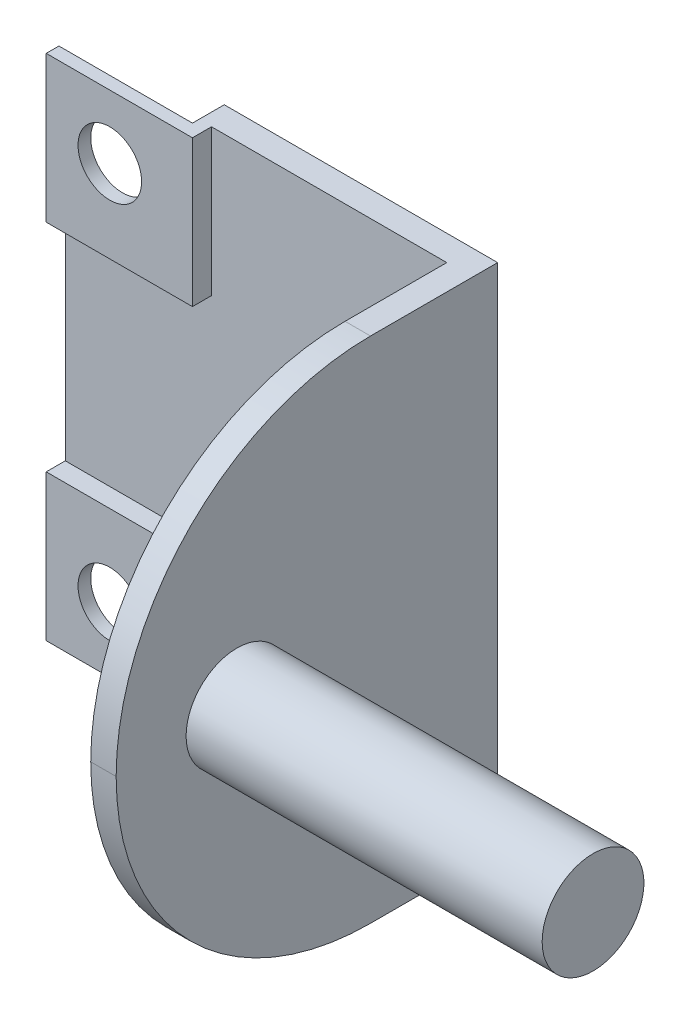
SolidWorks part; units mm, degrees
ref_plane "Plan de face" through (0, 0, 0) normal (0, 0, 1) x (1, 0, 0)
ref_plane "Plan de dessus" through (0, 0, 0) normal (0, 1, 0) x (1, 0, 0)
ref_plane "Plan de droite" through (0, 0, 0) normal (1, 0, 0) x (0, 0, -1)
sketch "Esquisse1" plane through (0, 0, 0) normal (0, 0, 1) x (1, 0, 0)
  line L1 (0, 0) -> (-32, 0)
  line L2 (0, 0) -> (0, 40)
  line L3 (0, 40) -> (-32, 40)
  line L4 (-32, 0) -> (-32, 40)
  dimension "D1" = 32
  dimension "D2" = 40
extrude "Boss.-Extru.1" add sketch "Esquisse1" along normal blind 2
sketch "Esquisse2" plane through (0, 0, 2) normal (0, 0, 1) x (1, 0, 0)
  line L0 (0, 40) -> (-32, 40) construction
  line L1 (0, 0) -> (-2, 0)
  line L2 (0, 0) -> (0, 40)
  line L3 (0, 40) -> (-2, 40)
  line L4 (-2, 0) -> (-2, 40)
  dimension "D1" = 2
extrude "Boss.-Extru.2" add sketch "Esquisse2" along normal blind 28
fillet "Congé1" radius 20 2 edges at (-1, 40, 30) (-1, 0, 30)
sketch "Esquisse3" plane through (0, 0, 0) normal (1, 0, 0) x (0, 0, -1)
  line L0 (0, 40) -> (0, 0) construction
  line L1 (-30, 20) -> (0, 20) construction
  circle A0 centre (-20.5, 20) radius 4
  dimension "D2" = 8
  dimension "D1" = 9.5
extrude "Enlèv. mat.-Extru.1" cut sketch "Esquisse3" against normal blind 30
sketch "Esquisse4" plane through (0, 0, 2) normal (0, 0, 1) x (1, 0, 0)
  line L0 (0, 20) -> (-32, 20) construction
  line L1 (-32, 40) -> (-21.5, 40)
  line L2 (-32, 40) -> (-32, 29.5)
  line L3 (-32, 29.5) -> (-21.5, 29.5)
  line L4 (-21.5, 40) -> (-21.5, 29.5)
  line L5 (-32, 40) -> (-32, 0) construction
  line L6 (-32, 10.5) -> (-21.5, 10.5)
  line L7 (-21.5, 0) -> (-21.5, 10.5)
  line L8 (-32, 0) -> (-21.5, 0)
  line L9 (-32, 0) -> (-32, 10.5)
  dimension "D1" = 10.5
  dimension "D2" = 10.5
extrude "Enlèv. mat.-Extru.2" cut sketch "Esquisse4" against normal blind 30
sketch "Esquisse5" plane through (0, 0, 2) normal (0, 0, 1) x (1, 0, 0)
  line L0 (0, 20) -> (-32, 20) construction
  line L1 (-21.5, 40) -> (-20.5, 40)
  line L2 (-21.5, 40) -> (-21.5, 28.5)
  line L3 (-21.5, 28.5) -> (-20.5, 28.5)
  line L4 (-20.5, 40) -> (-20.5, 28.5)
  line L5 (-32, 29.5) -> (-20.5, 29.5)
  line L6 (-32, 29.5) -> (-32, 28.5)
  line L7 (-32, 28.5) -> (-20.5, 28.5)
  line L8 (-20.5, 29.5) -> (-20.5, 28.5)
  line L9 (-32, 29.5) -> (-32, 10.5) construction
  line L10 (-21.5, 11.5) -> (-20.5, 11.5)
  line L11 (-20.5, 0) -> (-20.5, 11.5)
  line L12 (-21.5, 0) -> (-20.5, 0)
  line L13 (-21.5, 0) -> (-21.5, 11.5)
  line L14 (-32, 11.5) -> (-20.5, 11.5)
  line L15 (-20.5, 10.5) -> (-20.5, 11.5)
  line L16 (-32, 10.5) -> (-20.5, 10.5)
  line L17 (-32, 10.5) -> (-32, 11.5)
  line M7 (-21.5, 40) -> (-21.5, 29.5)
  line M8 (-21.5, 29.5) -> (-32, 29.5)
  line M9 (-32, 29.5) -> (-32, 10.5)
  line M10 (-32, 10.5) -> (-21.5, 10.5)
  line M11 (-21.5, 10.5) -> (-21.5, 0)
  line M12 (-21.5, 0) -> (-2, 0)
  line M14 (-2, 40) -> (-21.5, 40)
  dimension "D1" = 11.5
  dimension "D2" = 1
extrude "Boss.-Extru.5" add sketch "Esquisse5" along normal blind 1.5 contours L5 L2 L3 L4 | L7 L2 M9 M8 | L5 L4 M7 M14 | L13 L16 L11 L10 | L16 L11 M11 M12 | L14 L13 M9 M10 region at (-26.75, 11, 2) region at (-21, 34.75, 2) region at (-21, 29, 2) region at (-26.75, 29, 2) region at (-21, 11, 2) region at (-21, 5.25, 2)
sketch "Esquisse6" plane through (-21.5, 0, 0) normal (-1, 0, 0) x (0, 0, 1)
  line L0 (0, 29.5) -> (3.5, 29.5) construction
  line L1 (3.5, 40) -> (2.5, 40)
  line L2 (3.5, 40) -> (3.5, 29.5)
  line L3 (3.5, 29.5) -> (2.5, 29.5)
  line L4 (2.5, 40) -> (2.5, 29.5)
  line L5 (30, 20) -> (0, 20) construction
  line L6 (0, 29.5) -> (0, 10.5) construction
  line L7 (3.5, 10.5) -> (2.5, 10.5)
  line L8 (2.5, 0) -> (2.5, 10.5)
  line L9 (3.5, 0) -> (2.5, 0)
  line L10 (3.5, 0) -> (3.5, 10.5)
  dimension "D1" = 1
extrude "Boss.-Extru.6" add sketch "Esquisse6" along normal blind 10.5
sketch "Esquisse7" plane through (0, 0, 3.5) normal (0, 0, 1) x (1, 0, 0)
  line L0 (-32, 20) -> (0, 20) construction
  line L1 (-32, 28.5) -> (-32, 11.5) construction
  line L2 (-32, 40) -> (-22, 40) construction
  line L3 (-20.5, 40) -> (-32, 40) construction
  line L4 (-22, 40) -> (-22, 30) construction
  line L5 (-22, 30) -> (-32, 30) construction
  line L6 (-32, 40) -> (-32, 28.5) construction
  line L7 (-32, 30) -> (-32, 40) construction
  circle A0 centre (-27, 35) radius 2.5
  circle A1 centre (-27, 5) radius 2.5
  dimension "D5" = 5
  dimension "D1" = 10
  dimension "D2" = 10
  dimension "D3" = 5
  dimension "D4" = 5
extrude "Enlèv. mat.-Extru.3" cut sketch "Esquisse7" against normal blind 10.5
sketch "Esquisse8" plane through (-2, 0, 0) normal (-1, 0, 0) x (0, 0, 1)
  circle A0 centre (20.5, 20) radius 4
  dimension "D1" = 8
extrude "Boss.-Extru.7" add sketch "Esquisse8" against normal blind 30
